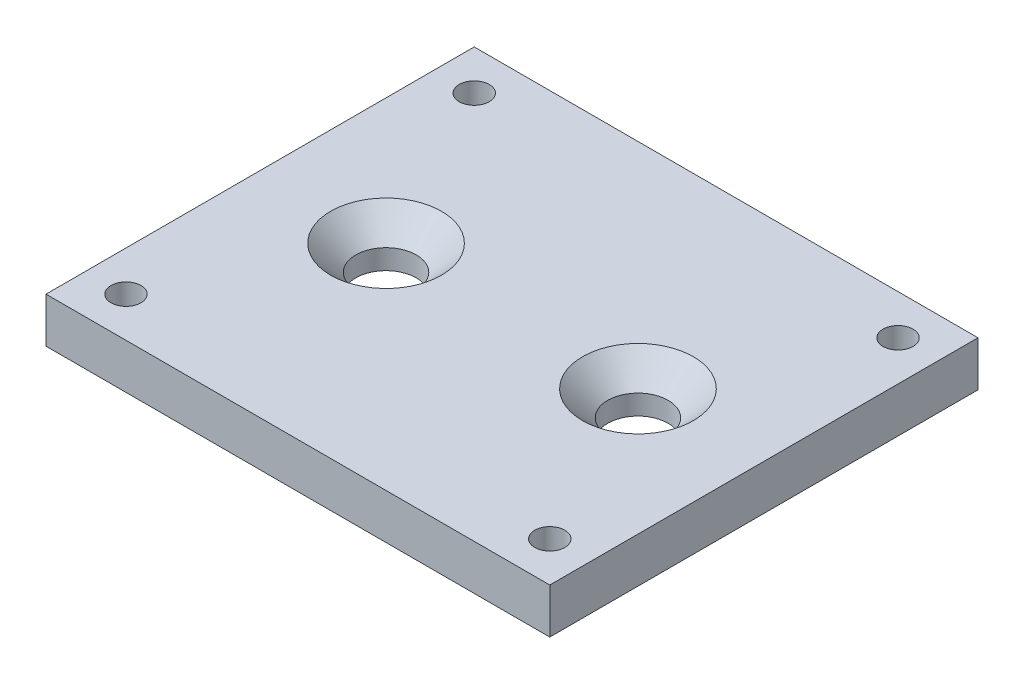
SolidWorks part; units mm, degrees
ref_plane "Front Plane" through (0, 0, 0) normal (0, 0, 1) x (1, 0, 0)
ref_plane "Top Plane" through (0, 0, 0) normal (0, 1, 0) x (1, 0, 0)
ref_plane "Right Plane" through (0, 0, 0) normal (1, 0, 0) x (0, 0, -1)
sketch "Sketch1" plane through (0, 0, 0) normal (0, 1, 0) x (1, 0, 0)
  line L1 (-10, -8.5) -> (10, -8.5)
  line L2 (-10, -8.5) -> (-10, 8.5)
  line L3 (-10, 8.5) -> (10, 8.5)
  line L4 (10, -8.5) -> (10, 8.5)
  line L5 (-10, -8.5) -> (10, 8.5) construction
  line L6 (-10, 8.5) -> (10, -8.5) construction
  point P0 (0, 0)
  dimension "D1" = 17
  dimension "D2" = 20
extrude "Boss-Extrude1" add sketch "Sketch1" along normal blind 1.7907
hole_wizard "#0-80 Tapped Hole1" positions "Sketch3" profile "Sketch2" tap size "#0-80" standard "Ansi Inch" end condition through all
sketch "Sketch3" plane through (0, 1.7907, 0) normal (0, 1, 0) x (-1, 0, 0)
  point P1 (-8.4125, -6.9125)
  point P4 (-8.4125, 6.9125)
  point P12 (8.4125, -6.9125)
  point P15 (8.4125, 6.9125)
sketch "Sketch2" plane through (8.4125, 1.7907, -6.9125) normal (1, 0, 0) x (0, 0, 1)
  line L0 (0, 0) -> (0, 1.7907)
  line L1 (0, 1.7907) -> (0.5956, 1.7907)
  line L2 (0.5956, 1.7907) -> (0.5956, 0)
  line L5 (0.5956, 0) -> (0, 0)
  line L11 (0, -6.35) -> (0, 107.95) construction
  dimension "Thread Major Dia." = 1.1913
  dimension "Thru Tap Drill Depth" = 1.7907
hole_wizard "CSK for M2 Flat Head Machine Screw1" positions "Sketch5" profile "Sketch4" countersink size "M2" standard "Ansi Metric" end condition through all
sketch "Sketch5" plane through (0, 1.7907, 0) normal (0, 1, 0) x (-1, 0, 0)
  line L0 (10, -8.5) -> (10, 8.5) construction
  line L1 (-10, 8.5) -> (-10, -8.5) construction
  point P0 (5, 0)
  point P1 (-5, 0)
  point P6 (10, 0)
  dimension "D1" = 5
  dimension "D2" = 5
sketch "Sketch4" plane through (-5, 1.7907, 0) normal (1, 0, 0) x (0, 0, 1)
  line L0 (0, 0) -> (0, 1.7907)
  line L1 (0, 1.7907) -> (1.2, 1.7907)
  line L2 (1.2, 1.7907) -> (1.2, 1)
  line L3 (1.2, 1) -> (2.2, 0)
  line L5 (2.2, 0) -> (0, 0)
  line L6 (-1.2, 1) -> (-2.2, 0) construction
  line L11 (0, -6.35) -> (0, 107.95) construction
  dimension "Thru Hole Dia." = 2.4
  dimension "Thru Hole Depth" = 1.7907
  dimension "Near C'Sink Dia." = 4.4
  dimension "Near C'Sink Angle" = 90
